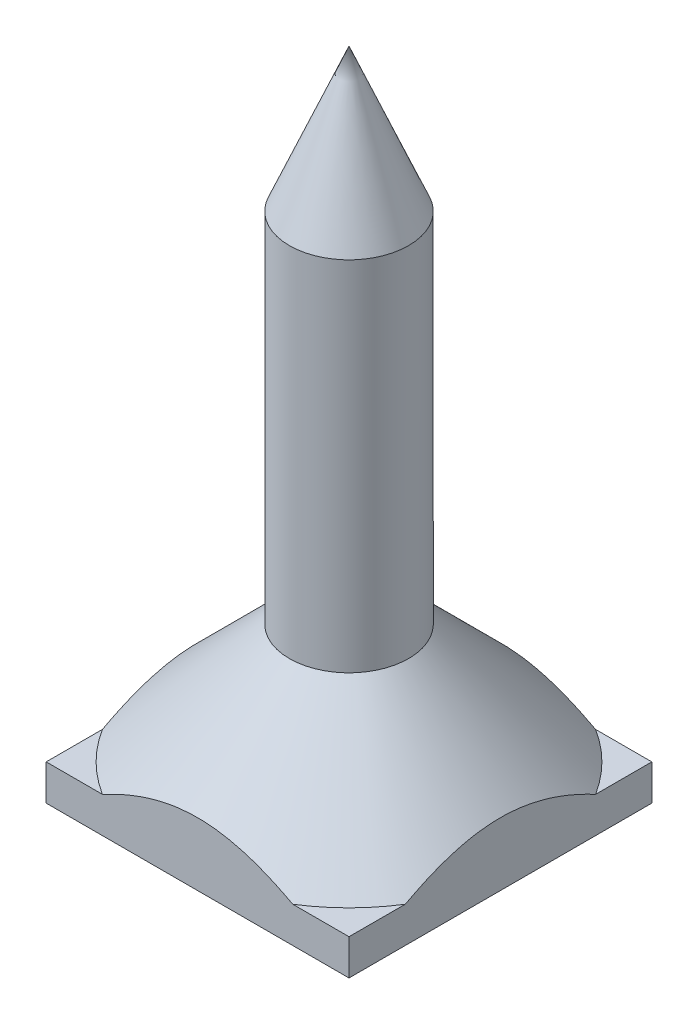
SolidWorks part; units mm, degrees
ref_plane "Front Plane" through (0, 0, 0) normal (0, 0, 1) x (1, 0, 0)
ref_plane "Top Plane" through (0, 0, 0) normal (0, 1, 0) x (1, 0, 0)
ref_plane "Right Plane" through (0, 0, 0) normal (1, 0, 0) x (0, 0, -1)
sketch "Sketch1" plane through (0, 0, 0) normal (0, 1, 0) x (1, 0, 0)
  line L1 (-12.7, 12.7) -> (12.7, 12.7)
  line L2 (-12.7, 12.7) -> (-12.7, -12.7)
  line L3 (-12.7, -12.7) -> (12.7, -12.7)
  line L4 (12.7, 12.7) -> (12.7, -12.7)
  line L5 (-12.7, 12.7) -> (12.7, -12.7) construction
  line L6 (-12.7, -12.7) -> (12.7, 12.7) construction
  point P0 (0, 0)
  dimension "D1" = 25.4
  dimension "D2" = 25.4
extrude "Boss-Extrude1" add sketch "Sketch1" along normal blind 3
sketch "Sketch2" plane through (0, 3, 0) normal (0, 1, 0) x (1, 0, 0)
  circle A0 centre (0, 0) radius 5
  dimension "D1" = 10
extrude "Boss-Extrude2" add sketch "Sketch2" along normal blind 40
chamfer "Chamfer1" distance 10 angle 45 1 edges at (0, 3, 5)
sketch "Sketch3" plane through (0, 0, 0) normal (1, 0, 0) x (0, 0, -1)
  line L0 (0, 0) -> (0, 52.5214) construction
  line L1 (5, 43) -> (0, 55)
  line L2 (5, 43) -> (-5, 43) construction
  line L3 (0, 55) -> (0, 43)
  line L4 (0, 43) -> (5, 43)
  line L5 (5, 43) -> (5.0421, 43.0676)
  dimension "D1" = 12
revolve "Revolve1" add sketch "Sketch3" angle 360 about L0 region at (0, 47, -1.6667)
